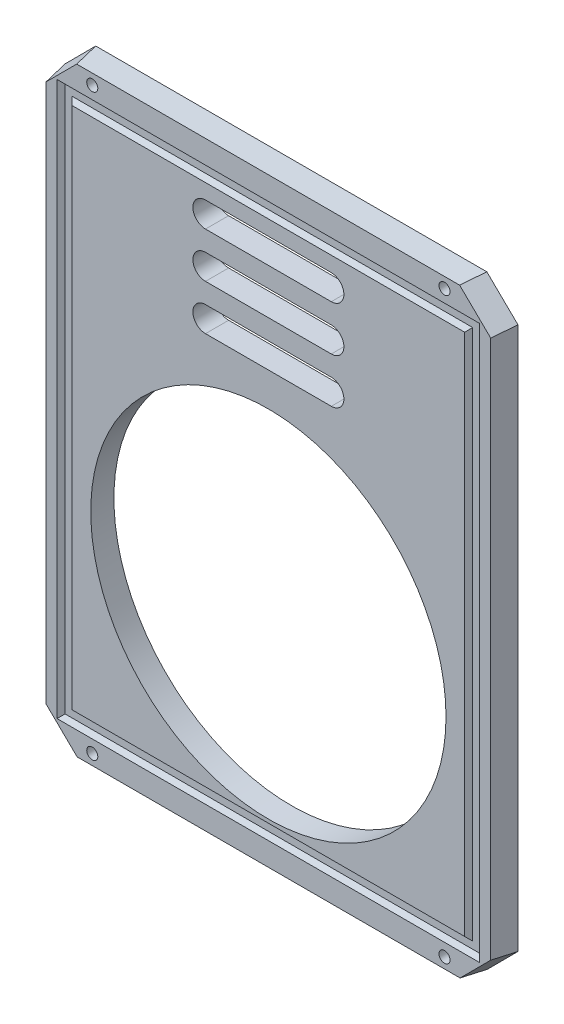
SolidWorks part; units mm, degrees
ref_plane "Front Plane" through (0, 0, 0) normal (0, 0, 1) x (1, 0, 0)
ref_plane "Top Plane" through (0, 0, 0) normal (0, 1, 0) x (1, 0, 0)
ref_plane "Right Plane" through (0, 0, 0) normal (1, 0, 0) x (0, 0, -1)
sketch "Sketch1" plane through (0, 0, 0) normal (0, 0, 1) x (1, 0, 0)
  line L1 (57.15, -76.2) -> (-57.15, -76.2)
  line L2 (57.15, -76.2) -> (57.15, 76.2)
  line L3 (57.15, 76.2) -> (-57.15, 76.2)
  line L4 (-57.15, -76.2) -> (-57.15, 76.2)
  line L5 (57.15, -76.2) -> (-57.15, 76.2) construction
  line L6 (57.15, 76.2) -> (-57.15, -76.2) construction
  line L12 (44.45, -73.025) -> (-44.45, -73.025) construction
  line L13 (44.45, -73.025) -> (44.45, 73.025) construction
  line L14 (44.45, 73.025) -> (-44.45, 73.025) construction
  line L15 (-44.45, -73.025) -> (-44.45, 73.025) construction
  line L16 (44.45, -73.025) -> (-44.45, 73.025) construction
  line L17 (44.45, 73.025) -> (-44.45, -73.025) construction
  circle A0 centre (0, -20.32) radius 44.831
  circle A1 centre (-44.45, 73.025) radius 1.397
  circle A2 centre (44.45, 73.025) radius 1.397
  circle A3 centre (44.45, -73.025) radius 1.397
  circle A4 centre (-44.45, -73.025) radius 1.397
  point P0 (0, 0)
  point P8 (0, 0)
  point P17 (0, 0)
  dimension "D3" = 89.662
  dimension "D6" = 2.794
  dimension "D1" = 152.4
  dimension "D2" = 114.3
  dimension "D4" = 20.32
  dimension "D5" = 88.9
  dimension "D7" = 146.05
extrude "Boss-Extrude1" add sketch "Sketch1" along normal blind 5.842
draft "Draft1" type of draft neutral plane draft angle 5 faces to draft 2 face at (0, 76.2, 2.921) face at (0, -76.2, 2.921) neutral plane through (0, 0, 0) neutral plane normal (0, 0, -1) reverse direction yes parameters "D1"=5
draft "Draft2" type of draft neutral plane draft angle 10 faces to draft 2 face at (57.15, 0, 2.921) face at (-57.15, 0, 2.921) neutral plane through (0, 0, 0) neutral plane normal (0, 0, -1) reverse direction yes parameters "D1"=10
sketch "Sketch2" plane through (0, 0, 5.842) normal (0, 0, 1) x (1, 0, 0)
  line L1 (50.8, -67.31) -> (-50.8, -67.31)
  line L2 (50.8, -67.31) -> (50.8, 67.31)
  line L3 (50.8, 67.31) -> (-50.8, 67.31)
  line L4 (-50.8, -67.31) -> (-50.8, 67.31)
  line L5 (50.8, -67.31) -> (-50.8, 67.31) construction
  line L6 (50.8, 67.31) -> (-50.8, -67.31) construction
  point P0 (0, 0)
  dimension "D1" = 134.62
  dimension "D2" = 101.6
extrude "Cut-Extrude-Thin1" cut sketch "Sketch2" against normal blind 1.016 thin thin type one direction wall 1.27
chamfer "Chamfer1" distance 1.27 angle 45 8 edges at (50.8, 0, 5.842) (0, -67.31, 5.842) (-50.8, 0, 5.842) (0, 67.31, 5.842) (0, 68.58, 5.842) (52.07, 0, 5.842) (-52.07, 0, 5.842) (0, -68.58, 5.842)
chamfer "Chamfer2" distance 7.62 angle 45 4 edges at (56.6349, 75.9444, 2.921) (-56.6349, 75.9444, 2.921) (56.6349, -75.9444, 2.921) (-56.6349, -75.9444, 2.921)
sketch "Sketch3" plane through (0, 0, 5.842) normal (0, 0, 1) x (1, 0, 0)
  line L1 (15.875, 55.88) -> (-15.875, 55.88)
  line L2 (15.875, 55.88) -> (15.875, 62.23) construction
  line L3 (15.875, 62.23) -> (-15.875, 62.23)
  line L4 (-15.875, 55.88) -> (-15.875, 62.23) construction
  line L5 (15.875, 55.88) -> (-15.875, 62.23) construction
  line L6 (15.875, 62.23) -> (-15.875, 55.88) construction
  line L7 (15.875, 44.45) -> (-15.875, 44.45)
  line L8 (15.875, 44.45) -> (15.875, 50.8) construction
  line L9 (15.875, 50.8) -> (-15.875, 50.8)
  line L10 (-15.875, 44.45) -> (-15.875, 50.8) construction
  line L11 (15.875, 44.45) -> (-15.875, 50.8) construction
  line L12 (15.875, 50.8) -> (-15.875, 44.45) construction
  line L13 (15.875, 33.02) -> (-15.875, 33.02)
  line L14 (15.875, 33.02) -> (15.875, 39.37) construction
  line L15 (15.875, 39.37) -> (-15.875, 39.37)
  line L16 (-15.875, 33.02) -> (-15.875, 39.37) construction
  line L17 (15.875, 33.02) -> (-15.875, 39.37) construction
  line L18 (15.875, 39.37) -> (-15.875, 33.02) construction
  arc A0 (15.875, 62.23) -> (15.875, 55.88) centre (15.875, 59.055) cw
  arc A1 (15.875, 50.8) -> (15.875, 44.45) centre (15.875, 47.625) cw
  arc A2 (15.875, 39.37) -> (15.875, 33.02) centre (15.875, 36.195) cw
  arc A3 (-15.875, 39.37) -> (-15.875, 33.02) centre (-15.875, 36.195) ccw
  arc A4 (-15.875, 50.8) -> (-15.875, 44.45) centre (-15.875, 47.625) ccw
  arc A5 (-15.875, 62.23) -> (-15.875, 55.88) centre (-15.875, 59.055) ccw
  point P0 (0, 59.055)
  point P5 (0, 47.625)
  point P10 (0, 36.195)
  dimension "D1" = 6.35
  dimension "D2" = 31.75
  dimension "D3" = 33.02
  dimension "D4" = 5.08
  dimension "D5" = 5.08
extrude "Cut-Extrude1" cut sketch "Sketch3" against normal blind 7.62
